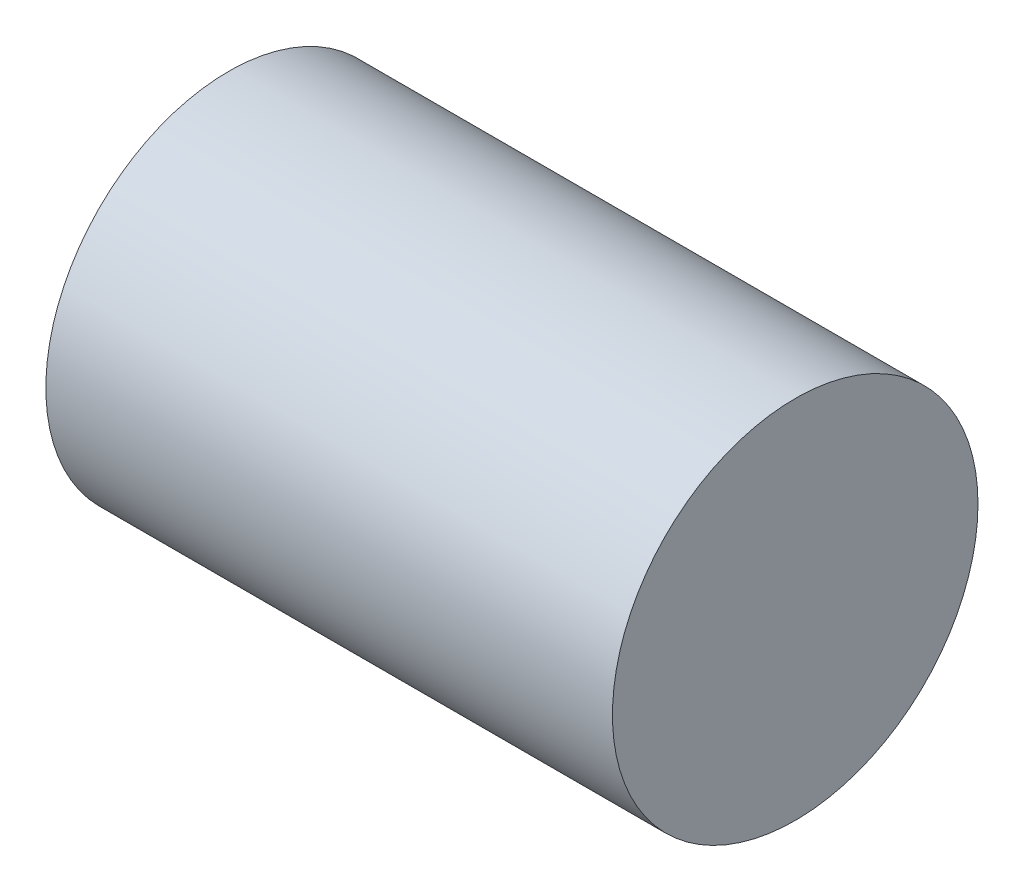
SolidWorks part; units mm, degrees
ref_plane "Front Plane" through (0, 0, 0) normal (0, 0, 1) x (1, 0, 0)
ref_plane "Top Plane" through (0, 0, 0) normal (0, 1, 0) x (1, 0, 0)
ref_plane "Right Plane" through (0, 0, 0) normal (1, 0, 0) x (0, 0, -1)
sketch "Sketch1" plane through (0, 0, 0) normal (1, 0, 0) x (0, 0, -1)
  circle A0 centre (0, 0) radius 76.2
  dimension "D1" = 152.4
extrude "Boss-Extrude1" add sketch "Sketch1" along normal blind 236.22
